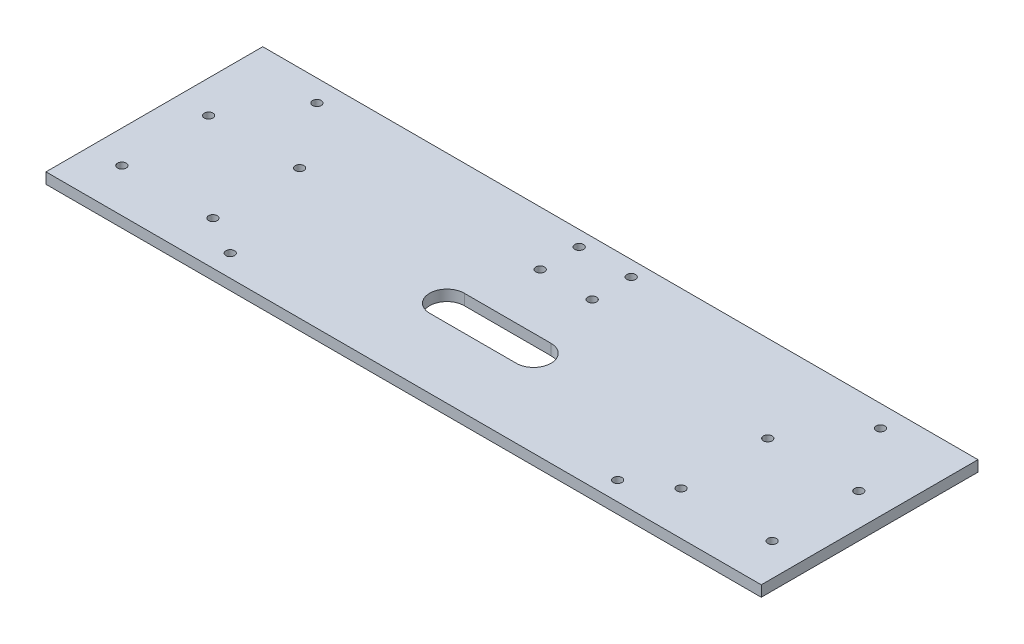
SolidWorks part; units mm, degrees
ref_plane "前视基准面" through (0, 0, 0) normal (0, 0, 1) x (1, 0, 0)
ref_plane "上视基准面" through (0, 0, 0) normal (0, 1, 0) x (1, 0, 0)
ref_plane "右视基准面" through (0, 0, 0) normal (1, 0, 0) x (0, 0, -1)
sketch "草图1" plane through (0, 0, 0) normal (0, 1, 0) x (1, 0, 0)
  line L1 (-155.3696, -90.2724) -> (174.6304, -90.2724)
  line L2 (-155.3696, -90.2724) -> (-155.3696, -190.2724)
  line L3 (-155.3696, -190.2724) -> (174.6304, -190.2724)
  line L4 (174.6304, -90.2724) -> (174.6304, -190.2724)
  dimension "D1" = 330
  dimension "D2" = 100
extrude "凸台-拉伸1" add sketch "草图1" along normal blind 5
sketch "草图3" plane through (0, 5, 0) normal (0, 1, 0) x (1, 0, 0)
  line L0 (9.6304, -73.8743) -> (9.6304, -261.3849) construction
  line L1 (-2.3696, -97.2724) -> (-2.3696, -133.7579) construction
  line L2 (174.6304, -90.2724) -> (-155.3696, -90.2724) construction
  circle A0 centre (-2.3696, -97.2724) radius 2
  circle A1 centre (21.6304, -97.2724) radius 2
  circle A2 centre (-2.3696, -115.2724) radius 2
  circle A3 centre (21.6304, -115.2724) radius 2
  point P13 (9.6304, -90.2724)
  dimension "D1" = 4
  dimension "D7" = 4
  dimension "D8" = 4
  dimension "D2" = 24
  dimension "D3" = 18
  dimension "D4" = 18
  dimension "D5" = 24
  dimension "D6" = 7
extrude "切除-拉伸1" cut sketch "草图3" against normal through all
sketch "草图4" plane through (0, 5, 0) normal (0, 1, 0) x (1, 0, 0)
  line L0 (-155.3696, -150.2724) -> (174.6304, -150.2724) construction
  line L1 (-155.3696, -90.2724) -> (-155.3696, -190.2724) construction
  line L2 (174.6304, -190.2724) -> (174.6304, -90.2724) construction
  line L3 (9.6304, -149.3208) -> (9.6304, -90.2724) construction
  line L4 (-10.3696, -150.2724) -> (29.6304, -150.2724) construction
  line L5 (-155.3696, -190.2724) -> (174.6304, -190.2724) construction
  line L6 (-10.3696, -142.2724) -> (29.6304, -142.2724)
  line L7 (-10.3696, -158.2724) -> (29.6304, -158.2724)
  circle A0 centre (-140.3696, -170.2724) radius 2
  circle A1 centre (-140.3696, -130.2724) radius 2
  circle A2 centre (-98.3696, -170.2724) radius 2
  circle A3 centre (-98.3696, -130.2724) radius 2
  circle A4 centre (117.6304, -130.2724) radius 2
  circle A5 centre (117.6304, -170.2724) radius 2
  circle A6 centre (159.6304, -130.2724) radius 2
  circle A7 centre (159.6304, -170.2724) radius 2
  arc A8 (-10.3696, -142.2724) -> (-10.3696, -158.2724) centre (-10.3696, -150.2724) ccw
  arc A9 (29.6304, -158.2724) -> (29.6304, -142.2724) centre (29.6304, -150.2724) ccw
  point P28 (9.6304, -150.2724)
  point P33 (9.6304, -150.2724)
  dimension "D1" = 4
  dimension "D3" = 42
  dimension "D8" = 8
  dimension "D9" = 4
  dimension "D2" = 20
  dimension "D4" = 15
  dimension "D5" = 40
  dimension "D6" = 20
  dimension "D7" = 20
extrude "切除-拉伸2" cut sketch "草图4" against normal through all
sketch "草图5" plane through (0, 5, 0) normal (0, 1, 0) x (1, 0, 0)
  line L0 (9.6304, -90.2724) -> (9.6304, 49909.7276) construction
  line L1 (174.6304, -90.2724) -> (-155.3696, -90.2724) construction
  line L2 (-155.3696, -190.2724) -> (174.6304, -190.2724) construction
  circle A0 centre (-120.3696, -100.2724) radius 2
  circle A1 centre (139.6304, -100.2724) radius 2
  circle A2 centre (-80.3696, -180.2724) radius 2
  circle A3 centre (99.6304, -181.5556) radius 2
  point P4 (9.6304, -90.2724)
  point P16 (0, 0)
  dimension "D1" = 4
  dimension "D3" = 10
  dimension "D4" = 10
  dimension "D5" = 90
  dimension "D2" = 130
  dimension "D6" = 90
extrude "切除-拉伸3" cut sketch "草图5" against normal through all
